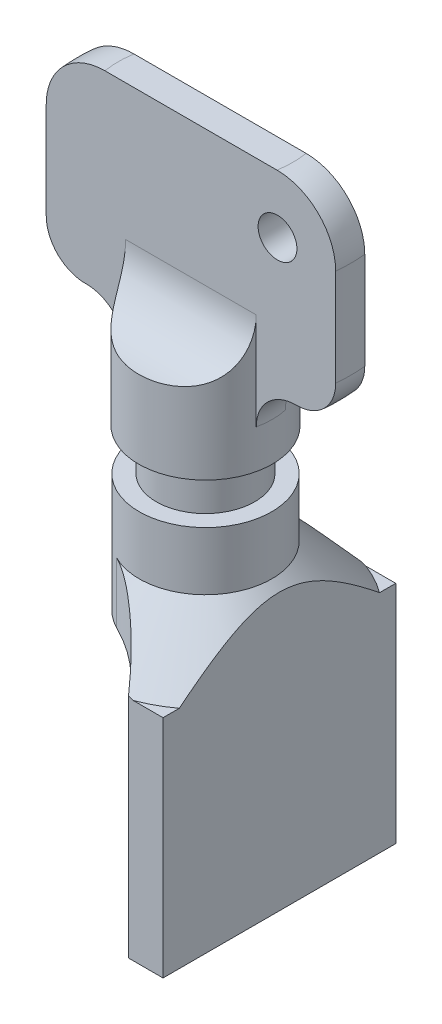
SolidWorks part; units mm, degrees
ref_plane "Front Plane" through (0, 0, 0) normal (0, 0, 1) x (1, 0, 0)
ref_plane "Top Plane" through (0, 0, 0) normal (0, 1, 0) x (1, 0, 0)
ref_plane "Right Plane" through (0, 0, 0) normal (1, 0, 0) x (0, 0, -1)
sketch "Sketch1" plane through (0, 0, 0) normal (0, 0, 1) x (1, 0, 0)
  line L0 (-3.4489, 37.7658) -> (-3.4489, 33.7658)
  line L1 (-3.4489, 33.7658) -> (-2.5348, 33.7658)
  line L2 (-2.5348, 33.7658) -> (-2.5348, 31.625)
  line L3 (-2.5348, 31.625) -> (-3.4177, 31.625)
  line L4 (-3.4177, 31.625) -> (-3.4177, 23)
  line L5 (-3.4177, 23) -> (0, 23)
  line L6 (-3.4489, 37.7658) -> (0, 37.7658)
  line L7 (0, 37.7658) -> (0, 23)
  dimension "D1" = 33.7658
  dimension "D2" = 2.1409
  dimension "D3" = 23
  dimension "D4" = 4
revolve "Revolve1" add sketch "Sketch1" angle 360 about L7
sketch "Sketch2" plane through (0, 37.7658, 0) normal (0, 1, 0) x (1, 0, 0)
  line L1 (-11.4046, 0.75) -> (11.4046, 0.75)
  line L2 (-11.4046, 0.75) -> (-11.4046, -0.75)
  line L3 (-11.4046, -0.75) -> (11.4046, -0.75)
  line L4 (11.4046, 0.75) -> (11.4046, -0.75)
  line L5 (-11.4046, 0.75) -> (11.4046, -0.75) construction
  line L6 (-11.4046, -0.75) -> (11.4046, 0.75) construction
  circle A0 centre (0, 0) radius 3.4489
  circle A1 centre (0, 0) radius 7.5
  circle M3 centre (0, 0) radius 3.4489
  dimension "D2" = 15
  dimension "D1" = 1.5
extrude "Boss-Extrude1" add sketch "Sketch2" along normal blind 10 contours L3 L1 M3 | L1 A1 L3 M3 | L3 A1 L1 M3 region at (-5.4544, 37.7658, 0) region at (0, 37.7658, 0) region at (5.4544, 37.7658, 0)
fillet "Fillet2" radius 2 4 edges at (7.5, 37.7658, 0) (-7.5, 37.7658, 0) (-3.4489, 37.7658, 0) (3.4489, 37.7658, 0)
fillet "Fillet3" radius 3 4 edges at (-7.5, 47.7658, 0) (7.5, 47.7658, 0) (0, 37.7658, -0.75) (0, 37.7658, 0.75)
sketch "Sketch3" plane through (0, 0, 0) normal (0, 0, 1) x (1, 0, 0)
  line L0 (-4.4371, 47.7658) -> (4.4371, 47.7658) construction
  line L1 (7.4624, 44.7658) -> (7.4624, 39.7658) construction
  circle A0 centre (4.4624, 44.7658) radius 1
  dimension "D1" = 2
  dimension "D2" = 3
  dimension "D3" = 3
extrude "Cut-Extrude1" cut sketch "Sketch3" against normal through all and the other way through all
sketch "Sketch4" plane through (0, 0, 0) normal (0, 0, 1) x (1, 0, 0)
  line L1 (2.03, 25.6253) -> (3.81, 25.6253)
  line L2 (2.03, 25.6253) -> (2.03, 14)
  line L3 (2.03, 14) -> (3.81, 14)
  line L4 (3.81, 25.6253) -> (3.81, 14)
  dimension "D1" = 1.78
  dimension "D2" = 2.03
  dimension "D3" = 14
  dimension "D4" = 1.78
extrude "Boss-Extrude2" add sketch "Sketch4" along normal blind 6 and the other way blind 6
chamfer "Chamfer1" distance 3 angle 45 1 edges at (3.4177, 25.6253, 0)
fillet "Fillet4" radius 10 2 edges at (2.03, 25.8127, -2.7495) (2.03, 25.8127, 2.7495)
chamfer "Chamfer2" distance 2.5 angle 45 3 edges at (0.4285, 23, -4.3248) (0.4285, 23, 4.3248) (-3.4177, 23, 0)
